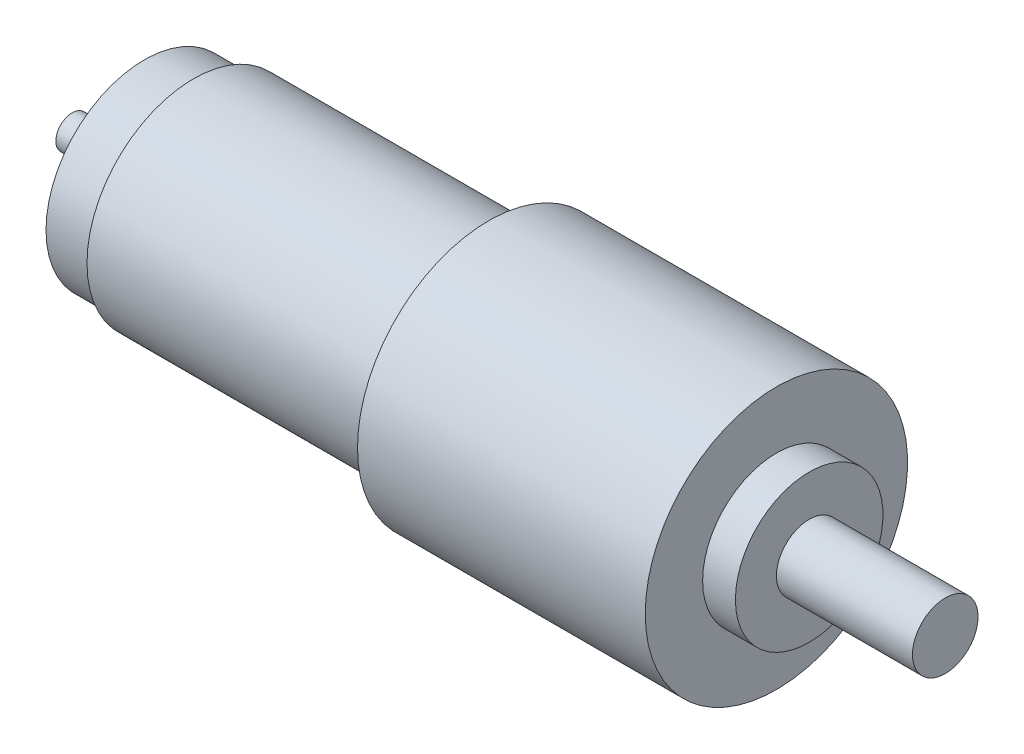
SolidWorks part; units mm, degrees
ref_plane "Plan de face" through (0, 0, 0) normal (0, 0, 1) x (1, 0, 0)
ref_plane "Plan de dessus" through (0, 0, 0) normal (0, 1, 0) x (1, 0, 0)
ref_plane "Plan de droite" through (0, 0, 0) normal (1, 0, 0) x (0, 0, -1)
sketch "Esquisse1" plane through (0, 0, 0) normal (0, 0, 1) x (1, 0, 0)
  line L0 (0, 0) -> (106.5, 0)
  line L1 (106.5, 0) -> (106.5, 4)
  line L2 (106.5, 4) -> (89.9, 4)
  line L3 (89.9, 4) -> (89.9, 9)
  line L4 (89.9, 9) -> (85.9, 9)
  line L5 (85.9, 9) -> (85.9, 16)
  line L6 (85.9, 16) -> (50.8, 16)
  line L7 (50.8, 16) -> (50.8, 13)
  line L8 (50.8, 13) -> (14.8, 13)
  line L9 (14.8, 13) -> (14.8, 12)
  line L10 (14.8, 12) -> (8.8, 12)
  line L11 (8.8, 12) -> (8.8, 2)
  line L12 (8.8, 2) -> (0, 2)
  line L13 (0, 2) -> (0, 0)
  dimension "D1" = 35.1
  dimension "D2" = 4
  dimension "D3" = 20.6
  dimension "D4" = 13
  dimension "D5" = 16
  dimension "D6" = 9
  dimension "D7" = 12
  dimension "D8" = 2
  dimension "D9" = 42
  dimension "D10" = 6
  dimension "D11" = 8.8
  dimension "D12" = 4
  dimension "D13" = 106.5
revolve "Révolution1" add sketch "Esquisse1" angle 360 about L0
